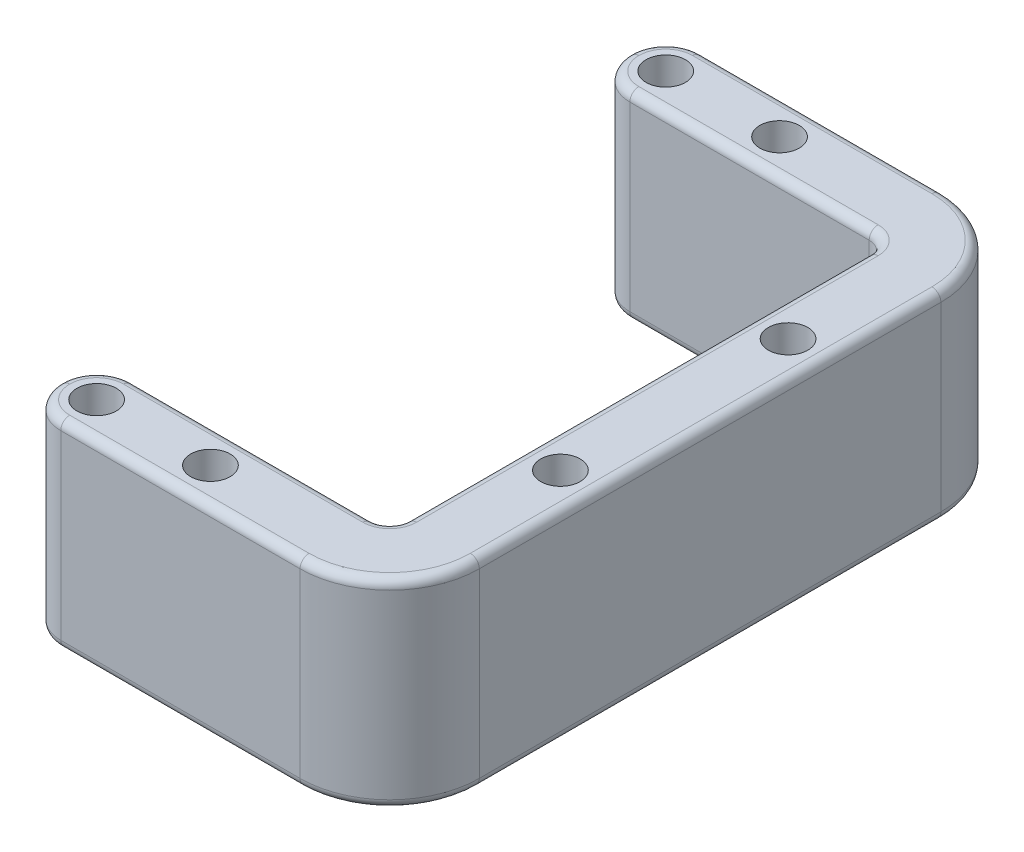
SolidWorks part; units mm, degrees
ref_plane "Front Plane" through (0, 0, 0) normal (0, 0, 1) x (1, 0, 0)
ref_plane "Top Plane" through (0, 0, 0) normal (0, 1, 0) x (1, 0, 0)
ref_plane "Right Plane" through (0, 0, 0) normal (1, 0, 0) x (0, 0, -1)
sketch "Sketch1" plane through (0, 0, 0) normal (0, 1, 0) x (1, 0, 0)
  line L1 (-4, 4) -> (28.7, 4)
  line L2 (-4, 4) -> (-4, -4)
  line L3 (-4, -4) -> (36.7, -4)
  line L8 (28.7, 4) -> (28.7, 59.5)
  line L9 (36.7, 67.5) -> (-4, 67.5)
  line L10 (36.7, 67.5) -> (36.7, -4)
  line L11 (28.7, 59.5) -> (-4, 59.5)
  line L12 (-4, 67.5) -> (-4, 59.5)
  circle A0 centre (0, 0) radius 2.2
  circle A1 centre (12.7, 0) radius 2.2
  circle A2 centre (12.7, 63.5) radius 2.2
  circle A3 centre (0, 63.5) radius 2.2
  circle A4 centre (32.7, 44.45) radius 2.2
  circle A5 centre (32.7, 19.05) radius 2.2
  point P9 (-4, 63.5)
  point P19 (28.7, 59.5)
  point P20 (28.7, 4)
  point P23 (0, 0)
  point P24 (28.7, 31.75)
  point P25 (0, 0)
  point P27 (-4, 0)
  dimension "D1" = 4.4
  dimension "D11" = 4
  dimension "D2" = 12.7
  dimension "D3" = 63.5
  dimension "D4" = 8
  dimension "D5" = 8
  dimension "D6" = 8
  dimension "D7" = 4
  dimension "D8" = 16
  dimension "D9" = 25.4
  dimension "D10" = 12.7
extrude "Boss-Extrude1" add sketch "Sketch1" along normal blind 22.2504 contours L9 L12 L11 L8 L1 L2 L3 L10 A3 A2 A1 A0 region at (12.35, 0, -3.1773)
fillet "Fillet1" radius 10 2 edges at (36.7, 11.1252, -67.5) (36.7, 11.1252, 4)
fillet "Fillet2" radius 2 2 edges at (28.7, 11.1252, -59.5) (28.7, 11.1252, -4)
fillet "Fillet3" radius 4 4 edges at (-4, 11.1252, -67.5) (-4, 11.1252, -59.5) (-4, 11.1252, -4) (-4, 11.1252, 4)
fillet "Fillet4" radius 1 28 edges at (-2.8284, 0, -2.8284) (13.35, 0, -4) (28.1142, 0, -4.5858) (28.7, 0, -31.75) (28.1142, 0, -58.9142) (13.35, 0, -59.5) (-2.8284, 0, -60.6716) (-2.8284, 0, -66.3284) (13.35, 0, -67.5) (33.7711, 0, -64.5711) (36.7, 0, -31.75) (-2.8284, 22.2504, -2.8284) (13.35, 22.2504, -4) (28.1142, 22.2504, -4.5858) (28.7, 22.2504, -31.75) (28.1142, 22.2504, -58.9142) (13.35, 22.2504, -59.5) (-2.8284, 22.2504, -60.6716) (-2.8284, 22.2504, -66.3284) (13.35, 22.2504, -67.5) (33.7711, 22.2504, -64.5711) (36.7, 22.2504, -31.75) (-2.8284, 0, 2.8284) (33.7711, 0, 1.0711) (-2.8284, 22.2504, 2.8284) (33.7711, 22.2504, 1.0711) (13.35, 0, 4) (13.35, 22.2504, 4)
